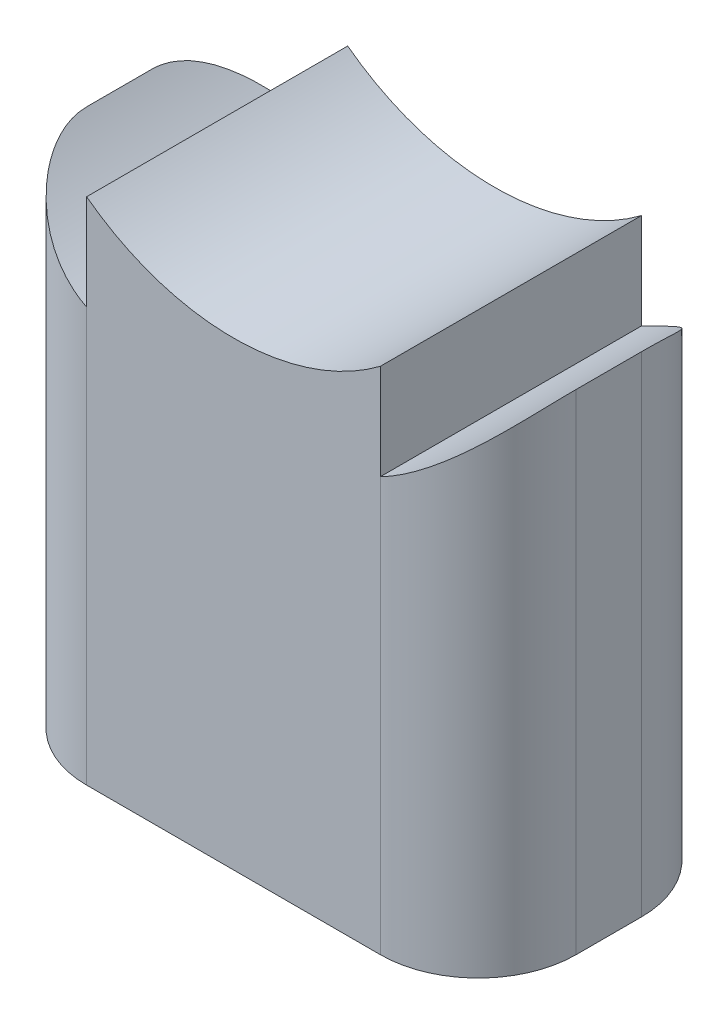
SolidWorks part; units mm, degrees
ref_plane "Alzado" through (0, 0, 0) normal (0, 0, 1) x (1, 0, 0)
ref_plane "Planta" through (0, 0, 0) normal (0, 1, 0) x (1, 0, 0)
ref_plane "Vista lateral" through (0, 0, 0) normal (1, 0, 0) x (0, 0, -1)
sketch "Sketch1" plane through (0, 0, 0) normal (0, 1, 0) x (1, 0, 0)
  line L1 (-45, -40) -> (45, -40)
  line L2 (-75, -10) -> (-75, 10)
  line L3 (-45, 40) -> (45, 40)
  line L4 (75, -10) -> (75, 10)
  line L5 (-75, -40) -> (75, 40) construction
  line L6 (-75, 40) -> (75, -40) construction
  arc A0 (-75, 10) -> (-45, 40) centre (-45, 10) cw
  arc A1 (45, -40) -> (75, -10) centre (45, -10) ccw
  arc A2 (-45, -40) -> (-75, -10) centre (-45, -10) cw
  arc A3 (45, 40) -> (75, 10) centre (45, 10) cw
  point P0 (0, 0)
  dimension "D3" = 30
  dimension "D4" = 30
  dimension "D1" = 150
  dimension "D2" = 80
extrude "Boss-Extrude1" add sketch "Sketch1" along normal blind 150
sketch "Sketch3" plane through (0, 0, 0) normal (0, 0, 1) x (1, 0, 0)
  line L0 (-75, 150) -> (-75, 0)
  line L5 (-75, 0) -> (-45, 0) construction
  line L6 (-75, 0) -> (75, 0)
  line L10 (75, 0) -> (75, 150)
  arc A3 (-75, 150) -> (75, 150) centre (0, 216.1438) ccw
  dimension "D1" = 100
extrude "Cut-Extrude1" cut sketch "Sketch3" against normal through all and the other way through all flip side to cut
sketch "Sketch4" plane through (0, 0, 40) normal (0, 0, 1) x (1, 0, 0)
  point P0 (0, 75)
  point P1 (0, 0)
  point P3 (0, 0)
  point P4 (0, 0)
  dimension "D1" = 75
sketch "Sketch5" plane through (0, 0, 40) normal (0, 0, 1) x (1, 0, 0)
  arc A0 (-45, 126.8409) -> (45, 126.8409) centre (0, 216.1438) ccw construction
  point P0 (0, 216.1438)
  point P4 (0, 0)
  point P5 (0, 0)
ref_axis "Axis1" through (0, 216.1438, 40) along (0, 0, 1)
sketch "Sketch6" plane through (0, 0, 40) normal (0, 0, 1) x (1, 0, 0)
  line L0 (0, 216.1438) -> (0, 116.1438) construction
  line L1 (-45, 126.8409) -> (-45, 156.1438)
  line L3 (45, 156.1438) -> (45, 126.8409)
  arc A0 (-45, 156.1438) -> (45, 156.1438) centre (0, 216.1438) ccw
  arc A1 (-45, 126.8409) -> (45, 126.8409) centre (0, 216.1438) ccw construction
  arc A2 (-45, 126.8409) -> (45, 126.8409) centre (0, 216.1438) ccw
  point P1 (0, 293.9455)
  point P14 (0, 0)
  dimension "D1" = 150
extrude "Boss-Extrude2" add sketch "Sketch6" against normal blind 80
